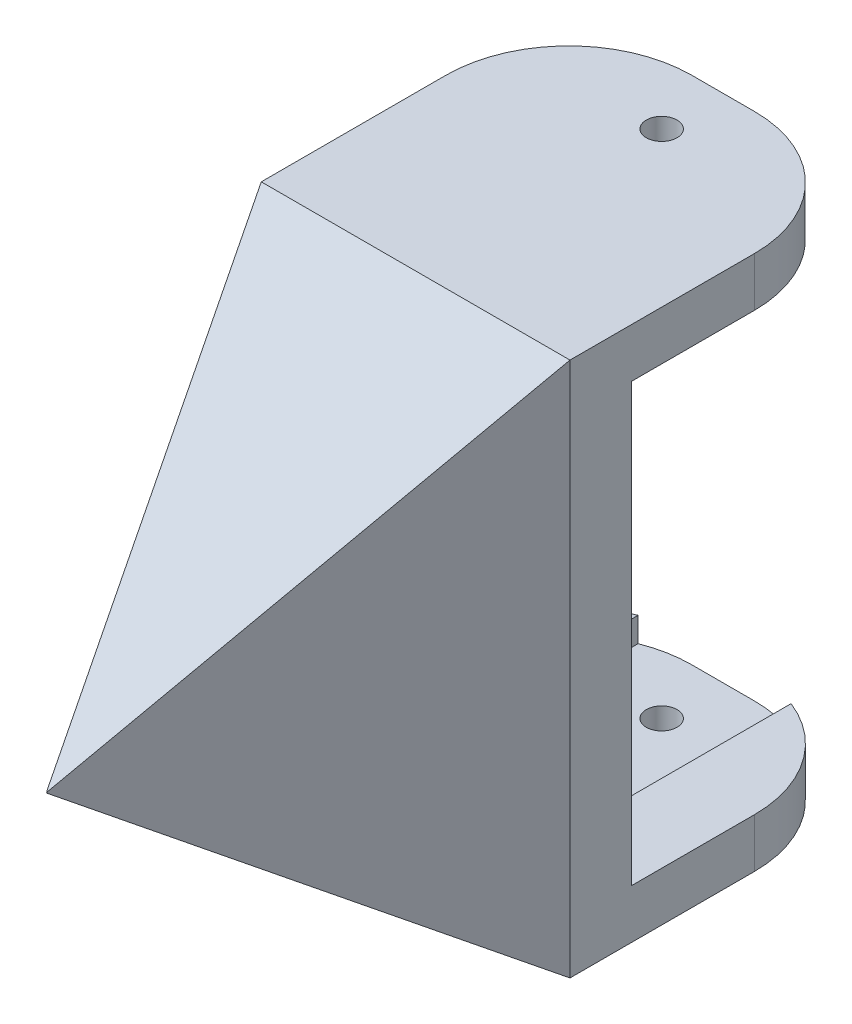
SolidWorks part; units mm, degrees
ref_plane "Front Plane" through (0, 0, 0) normal (0, 0, 1) x (1, 0, 0)
ref_plane "Top Plane" through (0, 0, 0) normal (0, 1, 0) x (1, 0, 0)
ref_plane "Right Plane" through (0, 0, 0) normal (1, 0, 0) x (0, 0, -1)
sketch "Sketch4" plane through (0, 0, 0) normal (0, 0, 1) x (1, 0, 0)
  line L1 (-6.23, -9.975) -> (6.23, -9.975)
  line L2 (-6.23, -9.975) -> (-6.23, 7.275)
  line L3 (-6.23, 7.275) -> (6.23, 7.275)
  line L4 (6.23, -9.975) -> (6.23, 7.275)
  point P4 (0, 7.275)
  dimension "D1" = 12.46
  dimension "D2" = 17.25
  dimension "D3" = 9.975
extrude "Boss-Extrude3" add sketch "Sketch4" along normal blind 6
sketch "Sketch8" plane through (0, -9.975, 0) normal (0, -1, 0) x (-1, 0, 0)
  circle A0 centre (0, -23.55) radius 12.5468
  circle A1 centre (0, -23.55) radius 11.15
  dimension "D1" = 22.3
  dimension "D2" = 23.55
extrude "Boss-Extrude6" add sketch "Sketch8" along normal blind 7.3 and the other way up to surface (17.25 mm away) other way up to face at (0, 7.275, 3)
sketch "Sketch5" plane through (0, 7.275, 0) normal (0, 1, 0) x (1, 0, 0)
  line L8 (12.5468, -23.55) -> (12.5468, 0)
  line L9 (12.5468, 0) -> (6.23, 0)
  line L10 (-12.5468, -23.55) -> (-12.5468, 0)
  line L11 (-12.5468, 0) -> (-6.23, 0)
  line L12 (-6.23, 0) -> (-6.23, -29.7)
  line L14 (6.23, -29.7) -> (6.23, 0)
  line L15 (-6.23, -29.7) -> (6.23, -29.7)
  line L16 (6.23, -6) -> (-6.23, -6) construction
  circle A0 centre (0, -23.55) radius 12.5468 construction
  arc A1 (-12.5468, -23.55) -> (12.5468, -23.55) centre (0, -23.55) ccw
  dimension "D1" = 23.7
  dimension "D2" = 23.55
extrude "Boss-Extrude4" add sketch "Sketch5" against normal up to surface (17.25 mm away) up to face at (0, -9.975, 3)
sketch "Sketch6" plane through (0, 7.275, 0) normal (0, 1, 0) x (1, 0, 0)
  line L0 (6.23, -6) -> (-6.23, -6) construction
  line L3 (6.23, -29.7) -> (-6.23, -29.7) construction
  circle A0 centre (0, -3.5) radius 2
  circle A1 centre (0, -32.2) radius 2
  dimension "D1" = 4
  dimension "D3" = 4
  dimension "D2" = 2.5
  dimension "D4" = 2.5
extrude "Cut-Extrude1" cut sketch "Sketch6" against normal blind 5
chamfer "Chamfer1" distance 0.5 angle 60 2 edges at (0, 7.275, 5.5) (0, 7.275, 34.2) first distance on face at (0, 7.275, 5.5)
sketch "Sketch10" plane through (0, 7.275, 0) normal (0, 1, 0) x (1, 0, 0)
  line L1 (-6.23, -6) -> (6.23, -6)
  line L2 (-6.23, -6) -> (-6.23, -29.7)
  line L3 (-6.23, -29.7) -> (6.23, -29.7)
  line L4 (6.23, -6) -> (6.23, -29.7)
extrude "Cut-Extrude3" cut sketch "Sketch10" against normal up to surface (17.25 mm away) up to face at (0, -9.975, 10.3399)
ref_plane "Plane1" through (0, 0, 36.0968) normal (0, 0, 1) x (1, 0, 0)
sketch "Sketch11" plane through (0, 0, 36.0968) normal (0, 0, 1) x (1, 0, 0)
  line L0 (-11.15, -9.975) -> (11.15, -9.975) construction
  line L1 (-2.5, -6.975) -> (2.5, -6.975)
  line L2 (-2.5, -6.975) -> (-2.5, -9.975)
  line L3 (-2.5, -9.975) -> (2.5, -9.975)
  line L4 (2.5, -6.975) -> (2.5, -9.975)
  point P4 (0, -6.975)
  dimension "D1" = 0
  dimension "D2" = 5
  dimension "D3" = 3
extrude "Cut-Extrude4" cut sketch "Sketch11" against normal up to next
sketch "Sketch13" plane through (0, -17.275, 0) normal (0, -1, 0) x (1, 0, 0)
  line L0 (-12.5468, 23.55) -> (-12.5468, 0)
  line L1 (-12.5468, 0) -> (12.5468, 0)
  line L2 (12.5468, 0) -> (12.5468, 23.55)
  arc A0 (-12.5468, 23.55) -> (12.5468, 23.55) centre (0, 23.55) ccw
  point P3 (0, 0)
extrude "Boss-Extrude7" add sketch "Sketch13" against normal up to surface (7.3 mm away) up to face at (0, -9.975, 10.3399)
sketch "Sketch15" plane through (0, 7.275, 0) normal (0, 1, 0) x (1, 0, 0)
  line L0 (-12.5468, 0) -> (12.5468, 0)
  line L1 (12.5468, 0) -> (12.5468, -23.55)
  line L2 (-12.5468, 0) -> (-12.5468, -23.55)
  line L3 (6.23, -6) -> (6.23, -29.7) construction
  line L4 (-6.23, -0.8) -> (6.23, -0.8)
  line L5 (-6.23, -0.8) -> (-6.23, -33.5)
  line L6 (-5.23, -34.5) -> (5.23, -34.5)
  line L7 (6.23, -0.8) -> (6.23, -33.5)
  arc A0 (-12.5468, -23.55) -> (12.5468, -23.55) centre (0, -23.55) ccw
  circle A1 centre (0, -3.5) radius 2 construction
  arc A2 (5.23, -34.5) -> (6.23, -33.5) centre (5.23, -33.5) ccw
  arc A3 (-6.23, -33.5) -> (-5.23, -34.5) centre (-5.23, -33.5) ccw
  point P15 (0, -0.8)
  dimension "D1" = 0.8
  dimension "D3" = 1
  dimension "D2" = 2.7
  dimension "D4" = 0
  dimension "D5" = 34.5
extrude "Boss-Extrude9" add sketch "Sketch15" along normal blind 10
sketch "Sketch17" plane through (-12.5468, 4.7282, 0) normal (1, 0, 0) x (0, -1, 0)
  line L0 (26.4782, 25) -> (26.4782, 0)
  line L1 (26.4782, 0) -> (-17.0218, 0)
  line L2 (-17.0218, 0) -> (-17.0218, 25)
  line L3 (-17.0218, 25) -> (-13.0218, 25)
  line L4 (-13.0218, 25) -> (-13.0218, 5)
  line L5 (-13.0218, 5) -> (22.4782, 5)
  line L6 (22.4782, 5) -> (22.4782, 25)
  line L7 (22.4782, 25) -> (26.4782, 25)
  point P2 (4.7282, 5)
  point P10 (4.7282, 0)
  dimension "D1" = 4
  dimension "D2" = 35.5
  dimension "D3" = 0
  dimension "D4" = 25
  dimension "D5" = 5
extrude "Boss-Extrude10" add sketch "Sketch17" along normal up to surface (25.0936 mm away) up to face at (12.5468, 0, 11.775)
sketch "Sketch18" plane through (0, -17.75, 0) normal (0, 1, 0) x (0, 0, 1)
  line L0 (-25, -12.5468) -> (-25, 12.5468) construction
  line L1 (-25, 6.2191) -> (-5, 6.2191)
  line L2 (-25, 6.2191) -> (-25, -6.2191)
  line L3 (-25, -6.2191) -> (-5, -6.2191)
  line L4 (-5, 6.2191) -> (-5, -6.2191)
  line L5 (-5, -12.5468) -> (-5, 12.5468) construction
  point P6 (-25, 0)
  point P7 (-25, 0)
  dimension "D1" = 0
extrude "Cut-Extrude5" cut sketch "Sketch18" against normal blind 2
sketch "Sketch19" plane through (0, -19.75, 0) normal (0, 1, 0) x (0, 0, 1)
  line L0 (-25, -12.5468) -> (-25, 12.5468) construction
  circle A0 centre (-20, 0) radius 1.25
  dimension "D1" = 2.5
  dimension "D2" = 5
extrude "Cut-Extrude6" cut sketch "Sketch19" against normal through all both and the other way through all
fillet "Fillet1" radius 10 4 edges at (12.5468, -19.75, -25) (-12.5468, -19.75, -25) (-12.5468, 19.75, -25) (12.5468, 19.75, -25)
ref_plane "Plane2" through (0, 0, 0) normal (1, 0, 0) x (0, 0, -1)
ref_plane "Plane3" through (0, 0, 0) normal (0, -1, 0) x (-1, 0, 0)
sketch "Sketch20" plane through (0, 17.275, 0) normal (0, 1, 0) x (1, 0, 0)
  line L1 (12.5468, 0) -> (-12.5468, 0)
  line L2 (12.5468, 0) -> (12.5468, -36.0968)
  line L3 (12.5468, -36.0968) -> (-12.5468, -36.0968)
  line L4 (-12.5468, 0) -> (-12.5468, -36.0968)
extrude "Cut-Extrude7" cut sketch "Sketch20" against normal through all both and the other way through all
sketch "Sketch21" plane through (0, 21.75, 0) normal (0, 1, 0) x (1, 0, 0)
  line L0 (12.5468, 0) -> (-0.0254, -30)
  line L1 (-0.0254, -30) -> (-12.5468, 0)
  line L2 (-12.5468, 0) -> (12.5468, 0)
  point P3 (-12.5468, -30)
  point P6 (0, -27.262)
  dimension "D1" = 30
extrude "Boss-Extrude11" add sketch "Sketch21" against normal up to vertex (43.5 mm away) up to point (-12.5468, -21.75, 0)
sketch "Sketch22" plane through (0, 0, 0) normal (1, 0, 0) x (0, 0, -1)
  line L13 (0, 21.75) -> (-30, 0.01)
  line L14 (-30, -21.75) -> (-30, 21.75) construction
  line L15 (-30, 0.01) -> (-30, 21.75)
  line L16 (-30, 21.75) -> (0, 21.75)
  line L17 (0, -21.75) -> (-30, -21.75)
  line L18 (-30, -21.75) -> (-30, -0.01)
  line L19 (-30, -0.01) -> (0, -21.75)
  point P7 (-44.8471, -21.75)
  point P9 (-30, -21.75)
  point P10 (-30, -21.75)
  dimension "D1" = 0.02
  dimension "D2" = 0.01
extrude "Cut-Extrude8" cut sketch "Sketch22" against normal through all both and the other way through all
sketch "Sketch23" plane through (0, 0, 0) normal (0, 0, -1) x (-1, 0, 0)
  line L0 (12.5468, 17.75) -> (0, 0)
  line L1 (0, 0) -> (12.5468, -21.75)
  line L2 (12.5468, -21.75) -> (12.5468, 17.75)
extrude "Cut-Extrude9" cut sketch "Sketch23" against normal through all both and the other way through all
